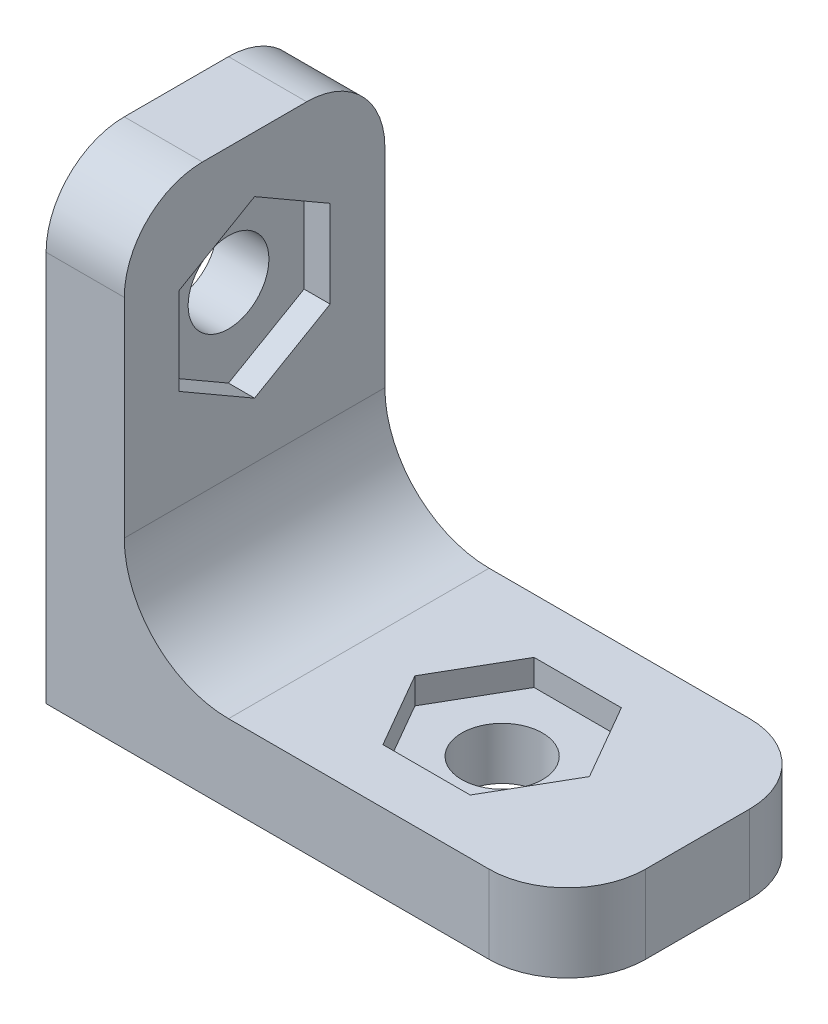
SolidWorks part; units mm, degrees
ref_plane "Alzado" through (0, 0, 0) normal (0, 0, 1) x (1, 0, 0)
ref_plane "Planta" through (0, 0, 0) normal (0, 1, 0) x (1, 0, 0)
ref_plane "Vista lateral" through (0, 0, 0) normal (1, 0, 0) x (0, 0, -1)
sketch "Croquis1" plane through (0, 0, 0) normal (0, 1, 0) x (1, 0, 0)
  line L1 (0, 0) -> (20, 0)
  line L2 (0, 0) -> (0, 10)
  line L3 (0, 10) -> (20, 10)
  line L4 (20, 0) -> (20, 10)
  circle A0 centre (12.5, 5) radius 1.55
  dimension "D3" = 3.1
  dimension "D1" = 20
  dimension "D2" = 10
  dimension "D4" = 12.5
  dimension "D5" = 5
extrude "Saliente-Extruir1" add sketch "Croquis1" along normal blind 3
sketch "Croquis2" plane through (0, 3, 0) normal (0, 1, 0) x (1, 0, 0)
  line L0 (0, 0) -> (20, 0) construction
  line L1 (0, 10) -> (3, 10)
  line L2 (0, 10) -> (0, 0)
  line L3 (0, 0) -> (3, 0)
  line L4 (3, 10) -> (3, 0)
  dimension "D1" = 3
extrude "Saliente-Extruir2" add sketch "Croquis2" along normal blind 15
sketch "Croquis3" plane through (0, 0, 0) normal (-1, 0, 0) x (0, 0, 1)
  line L0 (-10, 0) -> (0, 0) construction
  line L1 (0, 18) -> (0, 0) construction
  circle A0 centre (-5, 12.5) radius 1.55
  dimension "D1" = 3.1
  dimension "D2" = 12.5
  dimension "D3" = 5
extrude "Cortar-Extruir1" cut sketch "Croquis3" against normal up to surface (3 mm away) up to face at (3, 10.5, -5)
sketch "Croquis5" plane through (3, 0, 0) normal (1, 0, 0) x (0, 0, -1)
  line L1 (7.9, 14.1743) -> (5, 15.8486)
  line L2 (5, 15.8486) -> (2.1, 14.1743)
  line L3 (2.1, 14.1743) -> (2.1, 10.8257)
  line L4 (2.1, 10.8257) -> (5, 9.1514)
  line L5 (5, 9.1514) -> (7.9, 10.8257)
  line L6 (7.9, 10.8257) -> (7.9, 14.1743)
  line L8 (10, 18) -> (10, 3) construction
  circle A0 centre (5, 12.5) radius 2.9 construction
  dimension "D1" = 5.8
extrude "Cortar-Extruir3" cut sketch "Croquis5" against normal blind 1
fillet "Redondeo1" radius 3 4 edges at (1.5, 18, -10) (1.5, 18, 0) (20, 1.5, 0) (20, 1.5, -10)
fillet "Redondeo2" radius 4 1 edges at (3, 3, -5)
sketch "Croquis6" plane through (0, 3, 0) normal (0, 1, 0) x (1, 0, 0)
  line L0 (17, 10) -> (7, 10) construction
  line L1 (14.1743, 7.9) -> (10.8257, 7.9)
  line L2 (10.8257, 7.9) -> (9.1514, 5)
  line L3 (9.1514, 5) -> (10.8257, 2.1)
  line L4 (10.8257, 2.1) -> (14.1743, 2.1)
  line L5 (14.1743, 2.1) -> (15.8486, 5)
  line L6 (15.8486, 5) -> (14.1743, 7.9)
  circle A0 centre (12.5, 5) radius 2.9 construction
  dimension "D1" = 5.8
extrude "Cortar-Extruir4" cut sketch "Croquis6" against normal blind 1
